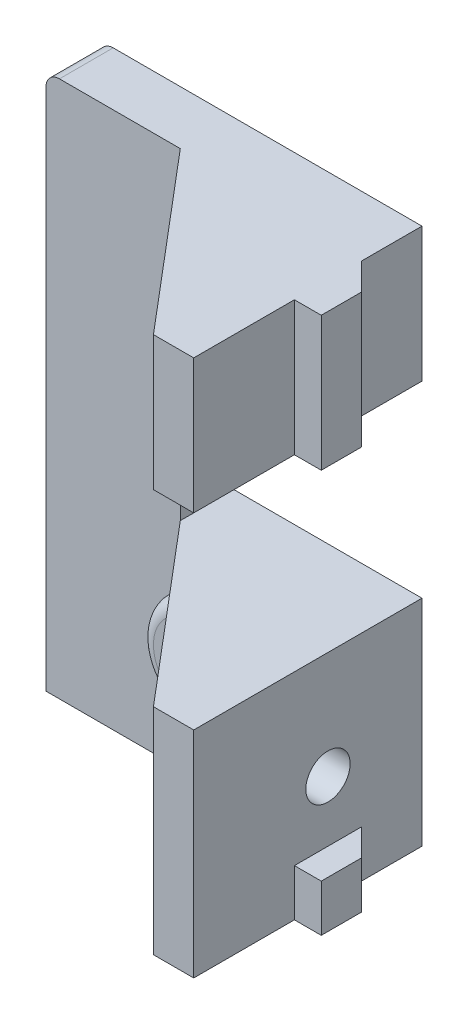
SolidWorks part; units mm, degrees
ref_plane "Front Plane" through (0, 0, 0) normal (0, 0, 1) x (1, 0, 0)
ref_plane "Top Plane" through (0, 0, 0) normal (0, 1, 0) x (1, 0, 0)
ref_plane "Right Plane" through (0, 0, 0) normal (1, 0, 0) x (0, 0, -1)
sketch "Sketch1" plane through (0, 0, 0) normal (0, 0, 1) x (1, 0, 0)
  line L1 (-26.7581, 33.2419) -> (-2.7581, 33.2419)
  line L2 (-26.7581, 33.2419) -> (-26.7581, -6.7581)
  line L3 (-26.7581, -6.7581) -> (-2.7581, -6.7581)
  line L4 (-2.7581, 33.2419) -> (-2.7581, -6.7581)
  dimension "D1" = 40
  dimension "D2" = 24
extrude "Boss-Extrude1" add sketch "Sketch1" along normal blind 4
fillet "Fillet1" radius 1 1 edges at (-26.7581, 33.2419, 2)
sketch "Sketch3" plane through (0, 0, 0) normal (0, 0, -1) x (-1, 0, 0)
  line L0 (2.7581, -6.7581) -> (2.7581, 33.2419) construction
  line L1 (2.7581, 9.2419) -> (16.7581, 9.2419)
  line L2 (2.7581, 9.2419) -> (2.7581, 23.2419)
  line L3 (2.7581, 23.2419) -> (16.7581, 23.2419)
  line L4 (16.7581, 9.2419) -> (16.7581, 23.2419)
  line L5 (26.7581, -6.7581) -> (2.7581, -6.7581) construction
  dimension "D1" = 14
  dimension "D2" = 14
  dimension "D3" = 16
extrude "Cut-Extrude2" cut sketch "Sketch3" against normal through all both and the other way through all
sketch "Sketch5" plane through (0, 0, 4) normal (0, 0, 1) x (1, 0, 0)
  line L0 (-26.7581, -6.7581) -> (-2.7581, -6.7581) construction
  line L1 (-2.7581, 9.2419) -> (-5.7581, 9.2419)
  line L2 (-2.7581, 9.2419) -> (-2.7581, -6.7581)
  line L3 (-2.7581, -6.7581) -> (-5.7581, -6.7581)
  line L4 (-5.7581, 9.2419) -> (-5.7581, -6.7581)
  dimension "D1" = 3
extrude "Boss-Extrude2" add sketch "Sketch5" along normal blind 13
sketch "Sketch6" plane through (0, -6.7581, 0) normal (0, -1, 0) x (1, 0, 0)
  line L0 (-5.7581, 17) -> (-16.6664, 4)
  line L1 (-26.7581, 4) -> (-5.7581, 4) construction
  line L2 (-16.6664, 4) -> (-5.7581, 4)
  line L3 (-5.7581, 4) -> (-5.7581, 17)
extrude "Boss-Extrude3" add sketch "Sketch6" against normal blind 3
sketch "Sketch7" plane through (0, 9.2419, 0) normal (0, 1, 0) x (1, 0, 0)
  line L0 (-5.7581, -17) -> (-16.7581, -4)
  line L1 (-16.7581, -4) -> (-5.7581, -4)
  line L2 (-5.7581, -4) -> (-5.7581, -17)
extrude "Boss-Extrude4" add sketch "Sketch7" against normal blind 3
sketch "Sketch8" plane through (-5.7581, 0, 0) normal (-1, 0, 0) x (0, 0, 1)
  line L0 (17, 6.2419) -> (17, -3.7581) construction
  line L1 (17, -6.7581) -> (4, -6.7581) construction
  circle A0 centre (7, 1.2419) radius 1.65
  dimension "D1" = 3.3
  dimension "D2" = 10
  dimension "D3" = 8
extrude "Cut-Extrude4" cut sketch "Sketch8" against normal blind 3
sketch "Sketch9" plane through (0, 0, 4) normal (0, 0, 1) x (1, 0, 0)
  line L0 (-16.7581, 23.2419) -> (-2.7581, 23.2419) construction
  line L1 (-2.7581, 33.2419) -> (-5.7581, 33.2419)
  line L2 (-2.7581, 33.2419) -> (-2.7581, 23.2419)
  line L3 (-2.7581, 23.2419) -> (-5.7581, 23.2419)
  line L4 (-5.7581, 33.2419) -> (-5.7581, 23.2419)
  dimension "D1" = 3
extrude "Boss-Extrude5" add sketch "Sketch9" along normal blind 13
sketch "Sketch10" plane through (0, 33.2419, 0) normal (0, 1, 0) x (1, 0, 0)
  line L0 (-5.7581, -17) -> (-16.7581, -4)
  line L1 (-16.7581, -4) -> (-5.7581, -4)
  line L2 (-5.7581, -4) -> (-5.7581, -17)
extrude "Boss-Extrude6" add sketch "Sketch10" against normal blind 6
sketch "Sketch11" plane through (-2.7581, 0, 0) normal (1, 0, 0) x (0, 0, -1)
  line L0 (-17, 33.2419) -> (0, 33.2419) construction
  line L1 (-9.5, 33.2419) -> (-4.5, 33.2419)
  line L2 (-9.5, 33.2419) -> (-9.5, 23.2419)
  line L3 (-9.5, 23.2419) -> (-4.5, 23.2419)
  line L4 (-4.5, 33.2419) -> (-4.5, 23.2419)
  line L5 (-17, 23.2419) -> (0, 23.2419) construction
  line L6 (-17, 23.2419) -> (-17, 33.2419) construction
  dimension "D1" = 5
  dimension "D2" = 7.5
extrude "Boss-Extrude7" add sketch "Sketch11" along normal blind 2
chamfer "Chamfer1" distance 2 angle 45 1 edges at (-0.7581, 28.2419, 4.5)
sketch "Sketch12" plane through (0, 0, 0) normal (0, 0, -1) x (-1, 0, 0)
  line L0 (26.7581, -6.7581) -> (2.7581, -6.7581) construction
  line L5 (2.7581, -6.7581) -> (2.7581, 9.2419) construction
  circle A0 centre (14.7581, 1.2419) radius 3.065
  dimension "D1" = 6.13
  dimension "D2" = 8
  dimension "D4" = 12
extrude "Cut-Extrude5" cut sketch "Sketch12" against normal blind 3.1
sketch "Sketch15" plane through (0, 0, 0) normal (0, 0, -1) x (-1, 0, 0)
  line L4 (26.7581, -6.7581) -> (2.7581, -6.7581) construction
  line L6 (16.7581, 23.2419) -> (16.7581, 9.2419) construction
  circle A0 centre (19.7581, 20.2419) radius 1.56
  point P4 (0, 0)
  point P7 (0, 0)
  dimension "D1" = 3.12
  dimension "D2" = 3
  dimension "D3" = 27
extrude "Cut-Extrude6" cut sketch "Sketch15" against normal blind 2.12
sketch "Sketch17" plane through (0, 0, 4) normal (0, 0, 1) x (1, 0, 0)
  circle A1 centre (-14.7581, 1.2419) radius 4
  dimension "D1" = 8
extrude "Boss-Extrude8" add sketch "Sketch17" along normal blind 1
fillet "Fillet3" radius 1 1 edges at (-10.7581, 1.2419, 5)
sketch "Sketch21" plane through (0, 0, 0) normal (0, 0, -1) x (-1, 0, 0)
  circle A0 centre (14.7581, 1.2419) radius 2.25
  dimension "D1" = 4.5
extrude "Boss-Extrude11" add sketch "Sketch21" against normal blind 2.9 separate body contours A0
sketch "Sketch23" plane through (-2.7581, 0, 0) normal (1, 0, 0) x (0, 0, -1)
  line L0 (-17, -6.7581) -> (0, -6.7581) construction
  line L1 (-9.5, -6.7581) -> (-4.5, -6.7581)
  line L2 (-9.5, -6.7581) -> (-9.5, -3.2581)
  line L3 (-9.5, -3.2581) -> (-4.5, -3.2581)
  line L4 (-4.5, -6.7581) -> (-4.5, -3.2581)
  dimension "D1" = 3.5
extrude "Boss-Extrude12" add sketch "Sketch23" along normal blind 2
chamfer "Chamfer2" distance 2 angle 45 1 edges at (-0.7581, -5.0081, 4.5)
fillet "Fillet5" radius 0.5 1 edges at (-21.3181, 20.2419, 0)
